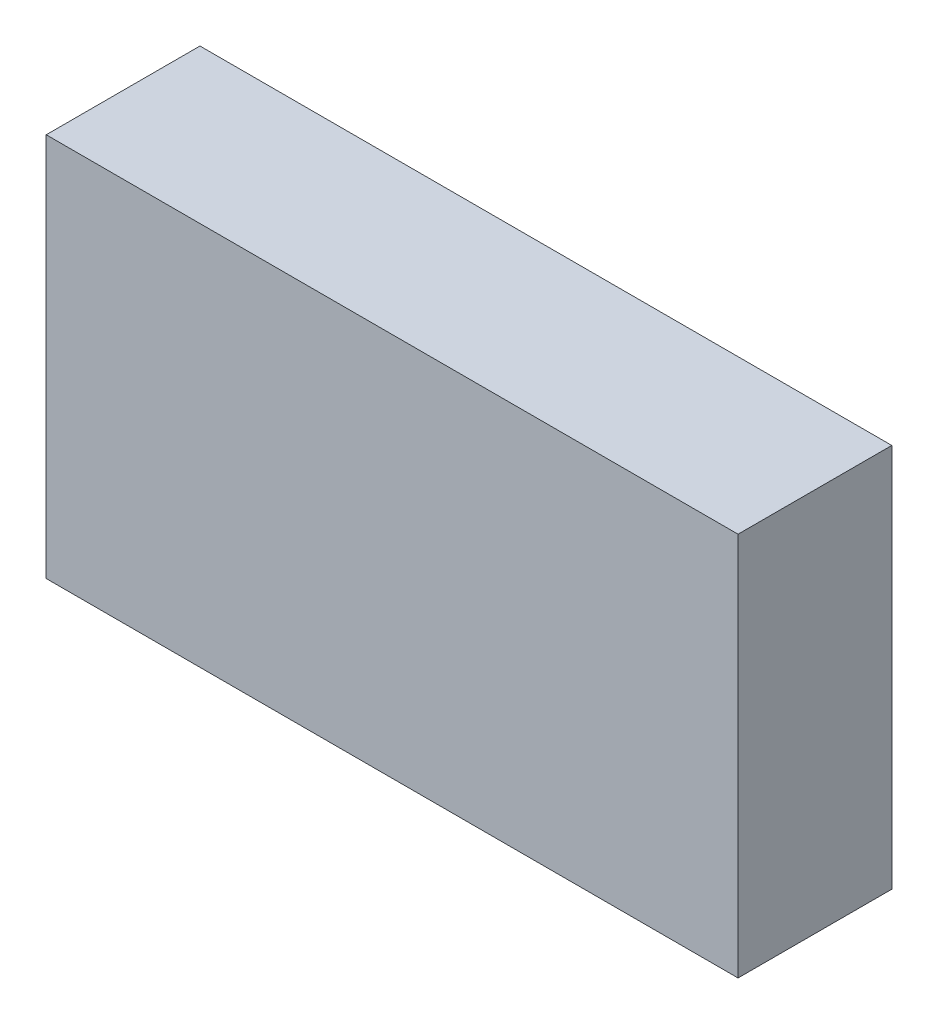
SolidWorks part; units mm, degrees
ref_plane "Ön Düzlem" through (0, 0, 0) normal (0, 0, 1) x (1, 0, 0)
ref_plane "Üst Düzlem" through (0, 0, 0) normal (0, 1, 0) x (1, 0, 0)
ref_plane "Sağ Düzlem" through (0, 0, 0) normal (1, 0, 0) x (0, 0, -1)
sketch "Çizim1" plane through (0, 0, 0) normal (0, 0, 1) x (1, 0, 0)
  line L1 (0, 0) -> (90, 0)
  line L2 (0, 0) -> (0, -50)
  line L3 (0, -50) -> (90, -50)
  line L4 (90, 0) -> (90, -50)
  dimension "D1" = 50
  dimension "D2" = 90
base flange "Taban-Flanş1" sketch "Çizim1" thickness 20 reverse thickness direction no parameters "D1"=4
sketch "Büküm-Çizgileri1" [suppressed] plane through (0, 0, 0) normal (0, 1, 0) x (1, 0, 0)
sketch "Sınırlandırma-Kutusu1" [suppressed] plane through (0, 0, 0) normal (0, 1, 0) x (1, 0, 0)
sheet metal parameters "Sac-Levha1" thickness 20 parameters "D1"=4
flat pattern "Düz-Çoğaltma1" [suppressed]
sketch "Büküm-Çizgileri2" plane through (0, 0, 0) normal (0, 1, 0) x (1, 0, 0)
sketch3d "Sınırlandırma-Kutusu2" [suppressed]
  line L0 (0, -50, 0) -> (90, -50, 0) construction
  line L1 (0, 0, 0) -> (90, 0, 0) construction
  line L2 (0, -50, 0) -> (0, 0, 0) construction
  line L3 (90, -50, 0) -> (90, 0, 0) construction
